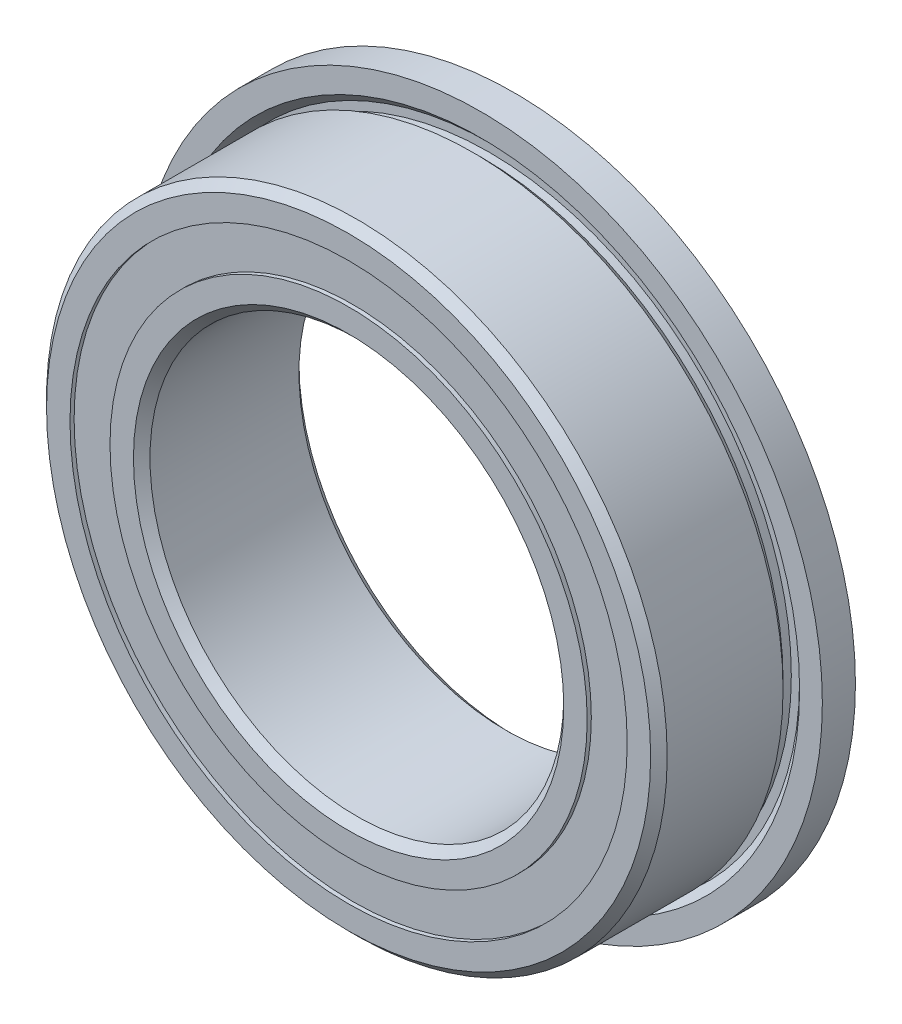
SolidWorks part; units mm, degrees
ref_plane "Front Plane" through (0, 0, 0) normal (0, 0, 1) x (1, 0, 0)
ref_plane "Top Plane" through (0, 0, 0) normal (0, 1, 0) x (1, 0, 0)
ref_plane "Right Plane" through (0, 0, 0) normal (1, 0, 0) x (0, 0, -1)
sketch "Sketch1" plane through (0, 0, 0) normal (0, 0, 1) x (1, 0, 0)
  circle A0 centre (0, 0) radius 5
  dimension "ID" = 10
sketch "Sketch2" plane through (0, 0, 0) normal (1, 0, 0) x (0, 0, -1)
  line L0 (-2, 0) -> (2, 0) construction
  line L1 (0, 7.5) -> (0, -7.5) construction
  line L2 (1.8, 7.5) -> (-1.8, 7.5) construction
  line L3 (-1.8, 7.5) -> (-2, 7.3)
  line L4 (-2, 7.3) -> (-2, 6.7335)
  line L5 (-2, 6.7335) -> (-0.8889, 6.7335)
  line L6 (2, 6.7335) -> (0.8889, 6.7335)
  line L7 (2, 7.3) -> (2, 6.7335)
  line L8 (1.8, 7.5) -> (2, 7.3) construction
  line L9 (0, 7.5) -> (0, 6.25) construction
  line L10 (0, 6.25) -> (0, 5) construction
  line L11 (1.2, 0) -> (1.2, 7.5) construction
  line L12 (2, 7.3) -> (2, 8.25)
  line L13 (2, 8.25) -> (1.2, 8.25)
  line L14 (1.2, 8.25) -> (1.2, 7.7)
  line L15 (1.2, 7.7) -> (1.4, 7.5)
  line L16 (1.4, 7.5) -> (1.4, 7.3)
  line L17 (1.4, 7.3) -> (1.2, 7.3)
  line L18 (1.2, 7.3) -> (1, 7.5)
  line L19 (-1.8, 7.5) -> (1, 7.5)
  line L20 (2, 8.25) -> (2, -8.25) construction
  line L21 (1.2, 7.5) -> (1.2, 7.7) construction
  line L22 (1.2, 7.5) -> (1, 7.5) construction
  line L23 (0, 5) -> (0, -5) construction
  arc A0 (-0.8889, 6.7335) -> (0.8889, 6.7335) centre (0, 6.25) cw
  point P14 (0, 5)
  point P15 (1.2, 0)
  point P25 (2, 0)
  point P29 (-1.8, -7.5)
  dimension "D1" = 45
  dimension "D2" = 0.2
  dimension "D3" = 1.7778
  dimension "D4" = 0.4835
  dimension "Flange Thickness" = 0.8
  dimension "Flange OD" = 16.5
  dimension "Width" = 4
  dimension "OD" = 15
sketch "Sketch7" plane through (0, 0, 0) normal (1, 0, 0) x (0, 0, -1)
  line L13 (2, 8.25) -> (1.2, 8.25)
  line L14 (1.2, 8.25) -> (1.2, 7.7)
  line L15 (1.2, 7.7) -> (1.4, 7.5)
  line L16 (1.4, 7.5) -> (1.4, 7.3)
  line L17 (1.4, 7.3) -> (1.2, 7.3)
  line L18 (1.2, 7.3) -> (1, 7.5)
  line L19 (1, 7.5) -> (-1.8, 7.5)
  line L20 (-1.8, 7.5) -> (-2, 7.3)
  line L21 (-2, 7.3) -> (-2, 6.7335)
  line L22 (-2, 6.7335) -> (-0.8889, 6.7335)
  line L23 (0.8889, 6.7335) -> (2, 6.7335)
  line L24 (2, 6.7335) -> (2, 7.3)
  line L25 (2, 7.3) -> (2, 8.25)
  line L26 (2, 8.25) -> (1.2, 8.25)
  line L27 (1.2, 8.25) -> (1.2, 7.7)
  line L28 (1.2, 7.7) -> (1.4, 7.5)
  line L29 (1.4, 7.5) -> (1.4, 7.3)
  line L30 (1.4, 7.3) -> (1.2, 7.3)
  line L31 (1.2, 7.3) -> (1, 7.5)
  line L32 (1, 7.5) -> (-1.8, 7.5)
  line L33 (-1.8, 7.5) -> (-2, 7.3)
  line L34 (-2, 7.3) -> (-2, 6.7335)
  line L35 (-2, 6.7335) -> (-0.8889, 6.7335)
  line L36 (0.8889, 6.7335) -> (2, 6.7335)
  line L37 (2, 6.7335) -> (2, 7.3)
  line L38 (2, 7.3) -> (2, 8.25)
  arc A1 (0.8889, 6.7335) -> (-0.8889, 6.7335) centre (0, 6.25) ccw
  arc A2 (0.8889, 6.7335) -> (-0.8889, 6.7335) centre (0, 6.25) ccw
  dimension "D1" = 0
revolve "Revolve7" add sketch "Sketch7" angle 360 about L0
sketch "Sketch3" plane through (0, 0, 0) normal (1, 0, 0) x (0, 0, -1)
  line L0 (-2, 5.7665) -> (-0.8889, 5.7665)
  line L1 (0, 7.5) -> (0, -7.5) construction
  line L2 (-2, 7.3) -> (-2, 6.7335) construction
  line L3 (-2, 5.7665) -> (-2, 5.2)
  line L4 (-1.8, 7.5) -> (-2, 7.3) construction
  line L5 (-2, 5.2) -> (-1.8, 5)
  line L6 (-1.8, 5) -> (1.8, 5)
  line L8 (1.8, 5) -> (2, 5.2)
  line L10 (2, 5.2) -> (2, 5.7665)
  line L11 (2, 5.7665) -> (0.8889, 5.7665)
  line L13 (1.8, 7.5) -> (2, 7.3) construction
  arc A0 (0.8889, 6.7335) -> (-0.8889, 6.7335) centre (0, 6.25) ccw construction
  arc A1 (0.8889, 5.7665) -> (-0.8889, 5.7665) centre (0, 6.25) cw
revolve "Revolve3" add sketch "Sketch3" angle 360 about L0
sketch "Sketch6" plane through (0, 0, 0) normal (1, 0, 0) x (0, 0, -1)
  line L1 (-0.0806, 6.4918) -> (0.0806, 6.4918)
  line L2 (-0.0806, 6.4918) -> (-0.0806, 6.0082)
  line L3 (-0.0806, 6.0082) -> (0.0806, 6.0082)
  line L4 (0.0806, 6.4918) -> (0.0806, 6.0082)
  line L5 (-0.0806, 6.4918) -> (0.0806, 6.0082) construction
  line L6 (-0.0806, 6.0082) -> (0.0806, 6.4918) construction
  point P4 (0, 6.25)
  dimension "D1" = 0.4835
  dimension "D2" = 0.1612
revolve "Revolve6" add sketch "Sketch6" angle 360 about L0
sketch "Sketch4" plane through (0, 0, 0) normal (1, 0, 0) x (0, 0, -1)
  line L0 (-1.0119, 6.25) -> (1.0119, 6.25)
  arc A2 (-1.0119, 6.25) -> (1.0119, 6.25) centre (0, 6.25) cw
  arc A3 (0.8889, 6.7335) -> (-0.8889, 6.7335) centre (0, 6.25) ccw construction
revolve "Revolve4" add sketch "Sketch4" angle 360 about L0
ref_axis "Axis1" through (0, 0, -2) along (0, 0, 1)
pattern_circular "CirPattern1" count 11 over 360 about axis through (0, 0, -2) along (0, 0, 1) of bodies 104
sketch "Sketch5" plane through (0, 0, 0) normal (1, 0, 0) x (0, 0, -1)
  line L0 (-2, 6.7335) -> (-0.8889, 6.7335) construction
  line L1 (-1.9, 6.7335) -> (-1.0119, 6.7335)
  line L2 (-1.9, 6.7335) -> (-1.9, 5.7665)
  line L3 (-1.9, 5.7665) -> (-1.0119, 5.7665)
  line L4 (-1.0119, 6.7335) -> (-1.0119, 5.7665)
  line L5 (-2, 5.7665) -> (-0.8889, 5.7665) construction
  line L6 (2, 6.7335) -> (0.8889, 6.7335) construction
  line L7 (1.9, 6.7335) -> (1.0119, 6.7335)
  line L8 (1.9, 6.7335) -> (1.9, 5.7665)
  line L9 (1.9, 5.7665) -> (1.0119, 5.7665)
  line L10 (1.0119, 6.7335) -> (1.0119, 5.7665)
  line L11 (2, 5.7665) -> (0.8889, 5.7665) construction
  line L12 (-1.8, 7.5) -> (-2, 7.3) construction
  point P18 (-1.9, 7.4)
revolve "Revolve5" add sketch "Sketch5" angle 360 about L0
equation "\"D2@Sketch2\" = \"Width@Sketch2\" * .05"
equation "\"D3@Sketch2\" = \"Width@Sketch2\" / 2.25"
equation "\"D4@Sketch2\" =  (  (  ( \"OD@Sketch2\" - \"Width@Sketch2\" )  / 2 )  / 3.25 )  / 3.5"
equation "\"D2@CirPattern1\" = 360/\"Balls@CirPattern1\""
equation "\"D1@Sketch6\" = \"D4@Sketch2\""
equation "\"D2@Sketch6\"=\"D1@Sketch6\"/3"
